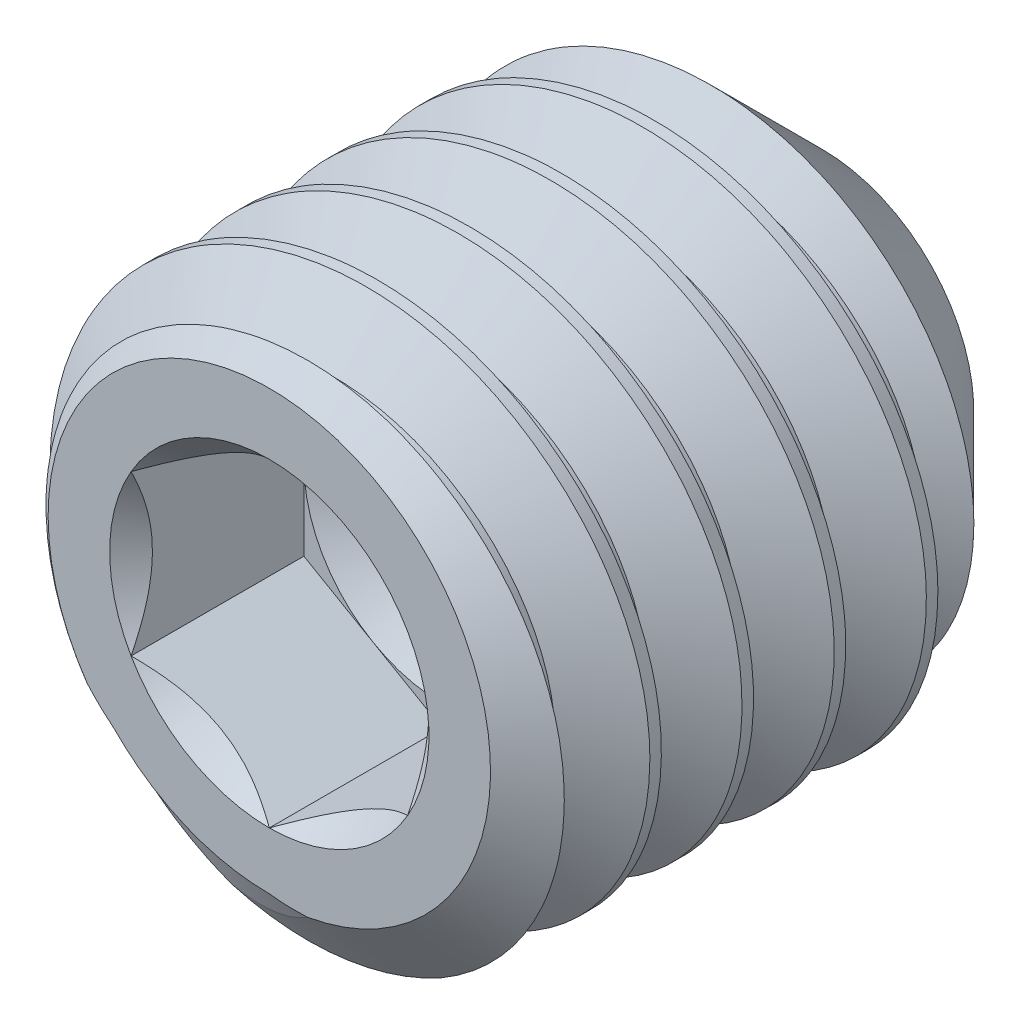
SolidWorks part; units mm, degrees
ref_plane "Front" through (0, 0, 0) normal (0, 0, 1) x (1, 0, 0)
ref_plane "Top" through (0, 0, 0) normal (0, 1, 0) x (1, 0, 0)
ref_plane "Right" through (0, 0, 0) normal (1, 0, 0) x (0, 0, -1)
sketch "Sketch22" plane through (0, 0, 0) normal (1, 0, 0) x (0, 0, -1)
  line L0 (-1.2531, 0) -> (-1.2531, 1.2)
  line L1 (-1.2531, 1.2) -> (-1.043, 1.5)
  line L2 (-1.043, 1.5) -> (1.0689, 1.5)
  line L3 (1.0689, 1.5) -> (1.7469, 0.8219)
  line L4 (1.7469, 0.8219) -> (1.2531, 0)
  line L5 (1.2531, 0) -> (-1.2531, 0)
  line L6 (1.2531, 0) -> (1.7469, 0) construction
  line L7 (1.7469, 0) -> (1.7469, 0.8219) construction
  line L8 (1.7469, -0.8219) -> (1.2531, 0) construction
  line L9 (-1.043, -1.5) -> (1.0689, -1.5) construction
  dimension "Dia" = 3
  dimension "Length" = 3
  dimension "D3" = 35
  dimension "D5" = 118
  dimension "D6" = 45
  dimension "D7" = 2.4
revolve "Revolve1" add sketch "Sketch22" angle 360 about L6
ref_plane "Plane1" through (0, 0, -1.7469) normal (0, 0, 1) x (1, 0, 0)
sketch "Sketch27" plane through (0, 0, -1.7469) normal (0, 0, 1) x (1, 0, 0)
  circle A0 centre (0, 0) radius 1.5 construction
  circle A1 centre (0, 0) radius 1.5
curve "Helix/Spiral1" pitch 0.5 height 3.5 turns 7
sketch "Sketch28" plane through (0, 0, 0) normal (1, 0, 0) x (0, 0, -1)
  line L0 (1.7469, 1.5) -> (2.1844, 1.5)
  line L1 (2.1844, 1.5) -> (1.9969, 1.1752)
  line L2 (1.9969, 1.1752) -> (1.9344, 1.1752)
  line L3 (1.9344, 1.1752) -> (1.7469, 1.5)
  line L4 (1.8407, 1.3376) -> (2.0907, 1.3376) construction
  line L6 (-1.043, 1.5) -> (1.0689, 1.5) construction
  dimension "D1" = 0.0625
  dimension "D2" = 0.25
  dimension "D3" = 60
sweep "Cut-Sweep2" cut profiles "Sketch28" path "Helix/Spiral1"
sketch "Sketch23" plane through (0, 0, 1.2531) normal (0, 0, 1) x (1, 0, 0)
  line L1 (0, 0.866) -> (-0.75, 0.433)
  line L2 (-0.75, 0.433) -> (-0.75, -0.433)
  line L3 (-0.75, -0.433) -> (0, -0.866)
  line L4 (0, -0.866) -> (0.75, -0.433)
  line L5 (0.75, -0.433) -> (0.75, 0.433)
  line L6 (0.75, 0.433) -> (0, 0.866)
  circle A0 centre (0, 0) radius 0.75 construction
  dimension "Hex" = 1.5
extrude "Cut-Extrude10" cut sketch "Sketch23" against normal blind 0.9375
sketch "Sketch24" plane through (0, 0, 1.2531) normal (0, 0, 1) x (1, 0, 0)
  circle A0 centre (0, 0) radius 0.866
extrude "Cut-Extrude11" cut sketch "Sketch24" against normal through all draft 45
sketch "Sketch26" plane through (0, 0, 0.3156) normal (0, 0, 1) x (1, 0, 0)
  circle A0 centre (0, 0) radius 0.75 construction
  circle A1 centre (0, 0) radius 0.75
extrude "Cut-Extrude12" cut sketch "Sketch26" against normal through all draft 60
sketch "Sketch30" plane through (0, 0, 0) normal (1, 0, 0) x (0, 0, -1)
  line L0 (-1.043, 1.5) -> (1.0689, 1.5) construction
  line L1 (-1.2531, 0) -> (-1.2531, 1.2) construction
  line L2 (1.7469, 0) -> (1.7469, 0.8219) construction
  line L3 (-1.043, -1.5) -> (1.0689, -1.5) construction
  point P0 (-1.2531, 1.5)
  point P1 (1.7469, 1.5)
  point P2 (1.7469, -1.5)
  point P11 (0.9969, -1.5)
  dimension "D1" = 0.75
sketch "Sketch31" plane through (0, 0, 0) normal (1, 0, 0) x (0, 0, -1)
  line L2 (1.2531, 0) -> (1.7469, -0.8219)
  line L3 (1.7469, 0.8219) -> (1.2531, 0)
equation "\"D7@Sketch22\"=\"Dia@Sketch22\"*.8"
equation "\"D1@Sketch28\" = \"D4@Helix/Spiral1\" * .125"
equation "\"D2@Sketch28\" = \"D4@Helix/Spiral1\" * .5"
equation "\"D3@Helix/Spiral1\" = \"Length@Sketch22\" + \"D4@Helix/Spiral1\""
equation "\"D1@Sketch30\" = \"D4@Helix/Spiral1\" * 1.5"
equation "\"hex Depth@Cut-Extrude10\" = \"Hex@Sketch23\" * .625"
